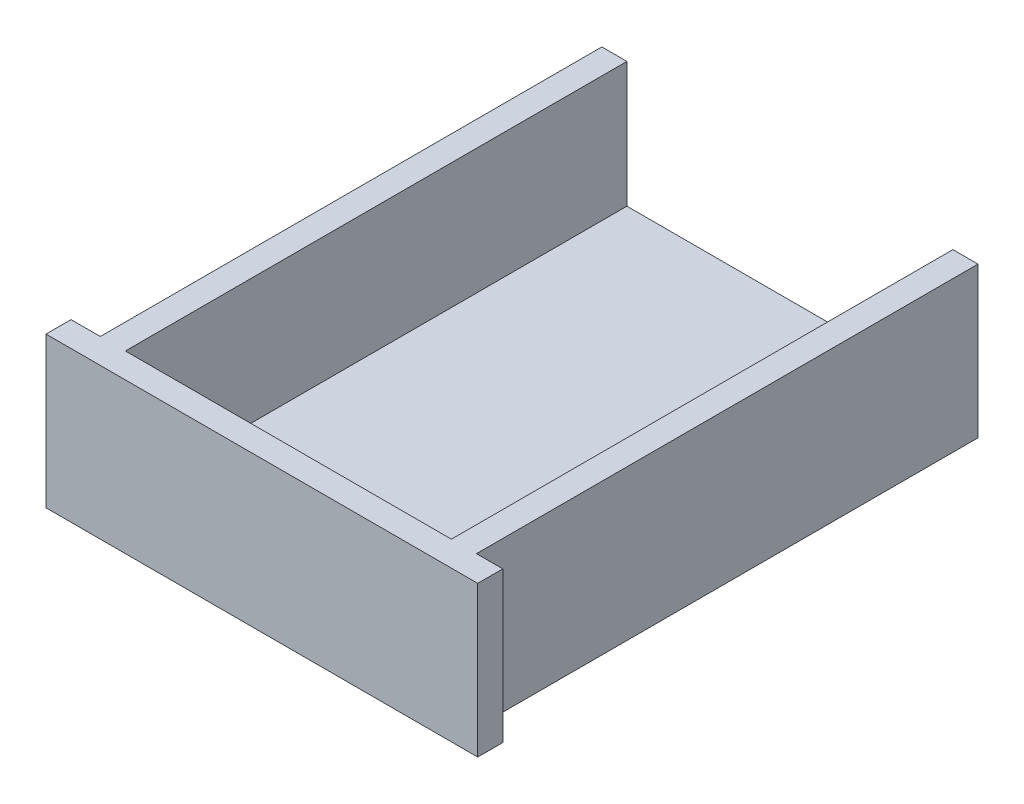
SolidWorks part; units mm, degrees
ref_plane "Front Plane" through (0, 0, 0) normal (0, 0, 1) x (1, 0, 0)
ref_plane "Top Plane" through (0, 0, 0) normal (0, 1, 0) x (1, 0, 0)
ref_plane "Right Plane" through (0, 0, 0) normal (1, 0, 0) x (0, 0, -1)
sketch "Sketch3" plane through (0, 0.0003, -31.967) normal (0, 0, 1) x (1, 0, 0)
  line L0 (106.7306, 145.4577) -> (106.7306, 86.6568) construction
  line L3 (99.2306, 85.6568) -> (114.2306, 85.6568)
  line L6 (100.2306, 86.6568) -> (113.2306, 86.6568)
  line L10 (99.2306, 85.6568) -> (99.2306, 91.6568)
  line L11 (99.2306, 91.6568) -> (100.2306, 91.6568)
  line L12 (100.2306, 86.6568) -> (100.2306, 91.6568)
  line L14 (114.2306, 85.6568) -> (114.2306, 91.6568)
  line L15 (114.2306, 91.6568) -> (113.2306, 91.6568)
  line L16 (113.2306, 86.6568) -> (113.2306, 91.6568)
  dimension "D3" = 1
  dimension "D5" = 1
  dimension "D6" = 5
extrude "Boss-Extrude1" add sketch "Sketch3" along normal up to surface (20 mm away)
sketch "Sketch4" plane through (0, 0.0001, -11.967) normal (0, 0, 1) x (1, 0, 0)
  line L0 (114.4806, 91.6568) -> (116.0806, 91.6568) construction
  line L1 (98.0647, 91.6568) -> (115.2806, 91.6568)
  line L2 (98.0647, 91.6568) -> (98.0647, 85.6568)
  line L3 (98.0647, 85.6568) -> (115.2806, 85.6568)
  line L4 (115.2806, 91.6568) -> (115.2806, 85.6568)
  line L8 (114.4806, 145.4575) -> (114.4806, 71.6475) construction
  line L14 (116.0806, 145.4575) -> (116.0806, 71.6475) construction
  line L15 (97.3806, 91.6568) -> (98.9806, 91.6568) construction
  line L16 (114.2306, 85.6568) -> (99.2306, 85.6568) construction
  line L17 (97.3806, 145.4576) -> (97.3806, 71.6476) construction
  line L18 (98.9806, 145.4576) -> (98.9806, 71.6476) construction
  line L22 (99.2306, 91.6568) -> (100.2306, 91.6568) construction
  point P8 (102.4267, 91.6568)
  point P11 (98.0647, 91.6568)
  point P22 (115.4159, 91.6568)
  point P23 (115.2806, 91.6568)
extrude "Boss-Extrude2" add sketch "Sketch4" along normal blind 1
sketch "Sketch6" plane through (0, 0.0001, -10.967) normal (0, 0, 1) x (1, 0, 0)
  line L0 (98.0647, 88.6568) -> (115.2806, 88.6568) construction
  line L1 (98.0647, 91.6568) -> (98.0647, 85.6568) construction
  line L2 (115.2806, 85.6568) -> (115.2806, 91.6568) construction
  line L3 (106.6727, 91.6568) -> (106.6727, 85.6568) construction
  line L4 (115.2806, 91.6568) -> (98.0647, 91.6568) construction
  line L5 (98.0647, 85.6568) -> (115.2806, 85.6568) construction
  line L6 (98.0647, 90.1568) -> (115.2806, 90.1568) construction
  line L7 (98.0647, 91.6568) -> (98.0647, 85.6568) construction
  line L8 (115.2806, 85.6568) -> (115.2806, 91.6568) construction
  dimension "D1" = 1.5
